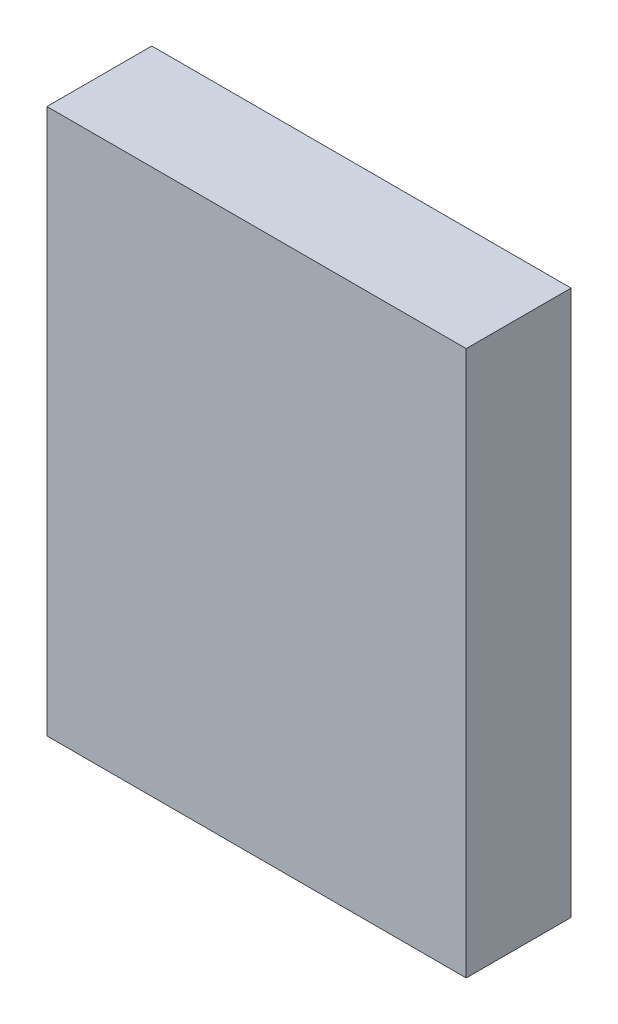
SolidWorks part; units mm, degrees
ref_plane "Front Plane" through (0, 0, 0) normal (0, 0, 1) x (1, 0, 0)
ref_plane "Top Plane" through (0, 0, 0) normal (0, 1, 0) x (1, 0, 0)
ref_plane "Right Plane" through (0, 0, 0) normal (1, 0, 0) x (0, 0, -1)
sketch "Sketch1" plane through (0, 0, 0) normal (0, 1, 0) x (1, 0, 0)
  line L1 (0, 0) -> (2, 0)
  line L2 (0, 0) -> (0, 0.5)
  line L3 (0, 0.5) -> (2, 0.5)
  line L4 (2, 0) -> (2, 0.5)
  dimension "D1" = 0.5
  dimension "D2" = 2
extrude "Boss-Extrude1" add sketch "Sketch1" along normal blind 2.6
